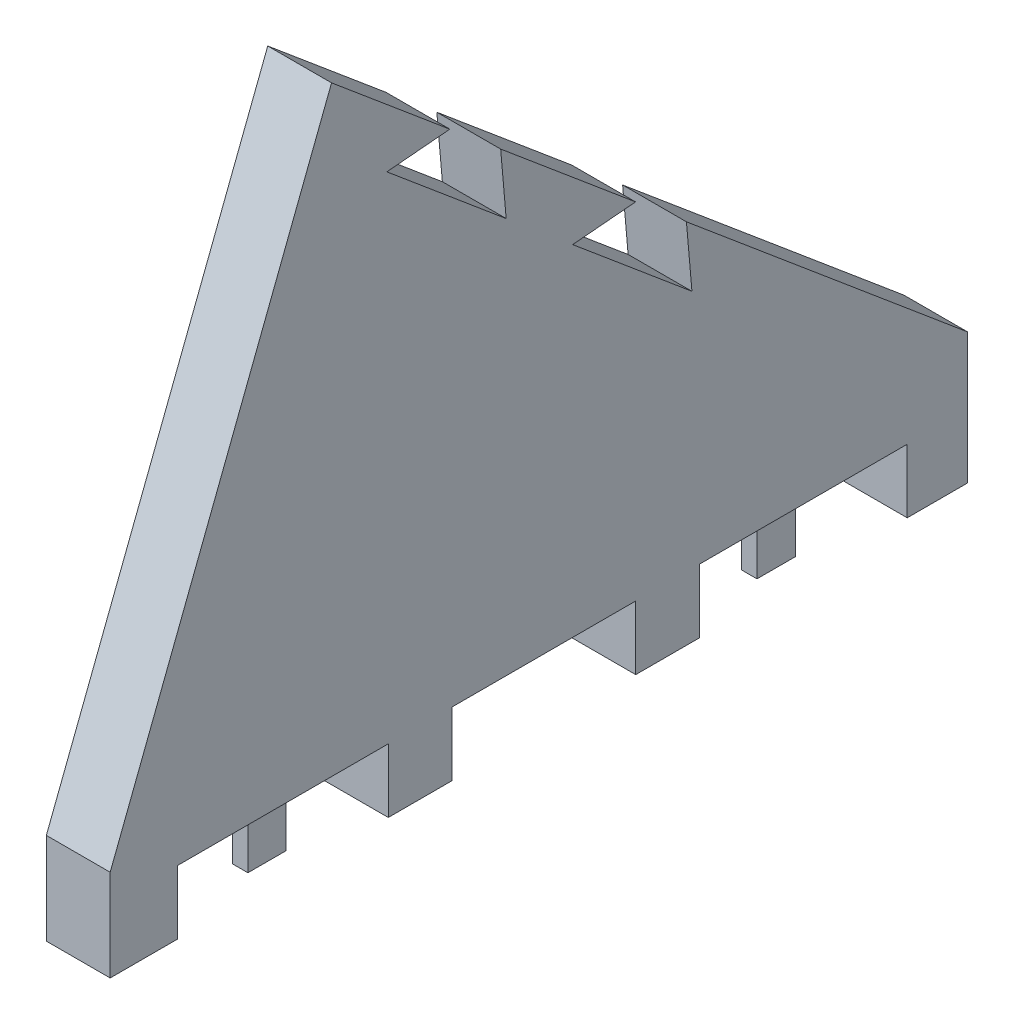
SolidWorks part; units mm, degrees
material "PVC 0.007 Plasticized"
ref_plane "Front Plane" through (0, 0, 0) normal (0, 0, 1) x (1, 0, 0)
ref_plane "Top Plane" through (0, 0, 0) normal (0, 1, 0) x (1, 0, 0)
ref_plane "Right Plane" through (0, 0, 0) normal (1, 0, 0) x (0, 0, -1)
sketch "Sketch2" plane through (0, 0, 0) normal (1, 0, 0) x (0, 0, -1)
  line L0 (12.1929, 0) -> (7.1929, 0)
  line L1 (-7.1929, 5) -> (7.1929, 5)
  line L3 (-12.1929, 0) -> (-12.1929, 4.9988)
  line L4 (-12.1929, 4.9988) -> (-18.4429, 4.9988)
  line L6 (18.4429, -0.0012) -> (21.4429, -0.0012)
  line L7 (12.1929, 0) -> (12.1929, 4.9988)
  line L8 (12.1929, 4.9988) -> (18.4429, 4.9988)
  line L10 (-12.1929, 0) -> (-7.1929, 0)
  line L13 (-7.1929, 0) -> (-7.1929, 5)
  line L17 (7.1929, 5) -> (7.1929, 0)
  line L18 (0, 55) -> (0, -55) construction
  line L19 (-28.6919, 0.0051) -> (-33.1993, 0.0051)
  line L23 (-18.4429, -0.0012) -> (-21.4429, -0.0012)
  line L24 (-18.4429, -0.0012) -> (-18.4429, 4.9988)
  line L26 (-21.4429, -0.0012) -> (-21.4429, 4.9988)
  line L27 (17.9531, 23.0454) -> (33.1993, 10.2523)
  line L28 (28.4653, 0.0051) -> (33.1993, 0.0051)
  line L29 (-3.3886, 40.9533) -> (7.1828, 32.0828)
  line L30 (21.4429, -0.0012) -> (21.4429, 4.9988)
  line L31 (18.4429, 4.9988) -> (21.4429, 4.9988)
  line L32 (18.4429, -0.0012) -> (18.4429, 4.9988)
  line L33 (21.4429, 4.9988) -> (27.8929, 4.9988)
  line L34 (-18.4429, 4.9988) -> (-21.4429, 4.9988)
  line L35 (-21.4429, 4.9988) -> (-27.8929, 4.9988)
  line L36 (2.2519, 31.6514) -> (7.1828, 32.0828)
  line L38 (33.1993, 0.0051) -> (33.1993, 10.2523)
  line L41 (-32.8929, 10.0051) -> (-16.6385, 52.0712)
  line L42 (-16.6385, 52.0712) -> (-7.3721, 44.2957)
  line L43 (11.1662, 28.7403) -> (14.8735, 25.6295)
  line L44 (-7.3721, 44.2957) -> (-12.303, 43.8643)
  line L45 (-12.303, 43.8643) -> (-2.9572, 36.0223)
  line L46 (-2.9572, 36.0223) -> (-3.3886, 40.9533)
  line L47 (11.5976, 23.8094) -> (2.2519, 31.6514)
  line L51 (11.1662, 28.7403) -> (11.5976, 23.8094)
  line L52 (-32.8929, 10.0051) -> (-33.9836, 7.1822)
  line L54 (1.8971, 36.518) -> (7.6818, 43.412) construction
  line L55 (14.8735, 25.6295) -> (17.9531, 23.0454)
  line L56 (-33.9836, 7.1822) -> (-33.9836, 0.0051)
  line L57 (-33.9836, 0.0051) -> (-33.1993, 0.0051)
  line L59 (-27.8929, 4.9988) -> (-28.6919, 4.9988)
  line L60 (-28.6919, 4.9988) -> (-28.6919, 0.0051)
  line L61 (27.8929, 4.9988) -> (28.4653, 4.9988)
  line L62 (28.4653, 4.9988) -> (28.4653, 0.0051)
  point P4 (0, 0)
  point P17 (-20.3929, 5)
  point P30 (0, 0)
  dimension "D2" = 15.7
  dimension "D3" = 130
  dimension "D4" = 5
  dimension "D5" = 12.2
  dimension "D6" = 45
  dimension "D7" = 5
  dimension "D8" = 6.9
  dimension "D9" = 4.8395
  dimension "D10" = 3
  dimension "D11" = 5
  dimension "D12" = 45
  dimension "D13" = 5.2
  dimension "D14" = 5.2
  dimension "D15" = 45
  dimension "D16" = 12.2
  dimension "D17" = 45
  dimension "D18" = 5
  dimension "D19" = 4.0202
  dimension "D20" = 19.9025
  dimension "D21" = 288.873
extrude "Boss-Extrude2" add sketch "Sketch2" along normal blind 5 contours L29 L46 L45 L44 L42 L41 L35 L26 L23 L24 L4 L3 L10 L13 L1 L17 L0 L7 L8 L32 L6 L30 L33 L28 L38 L27 | L19 region at (0, 19.3068, 4.3401)
extrude "Boss-Extrude3" add sketch "Sketch2<4>" along normal blind 1.2 from offset 2.05 contours L32 L6 L30 L31 | L24 L34 L26 L23 region at (0, 2.4988, -19.9429) region at (0, 2.4988, 19.9429)
sketch "Sketch2<4>" plane through (0, 0, 0) normal (1, 0, 0) x (0, 0, -1) same geometry as "Sketch2"
